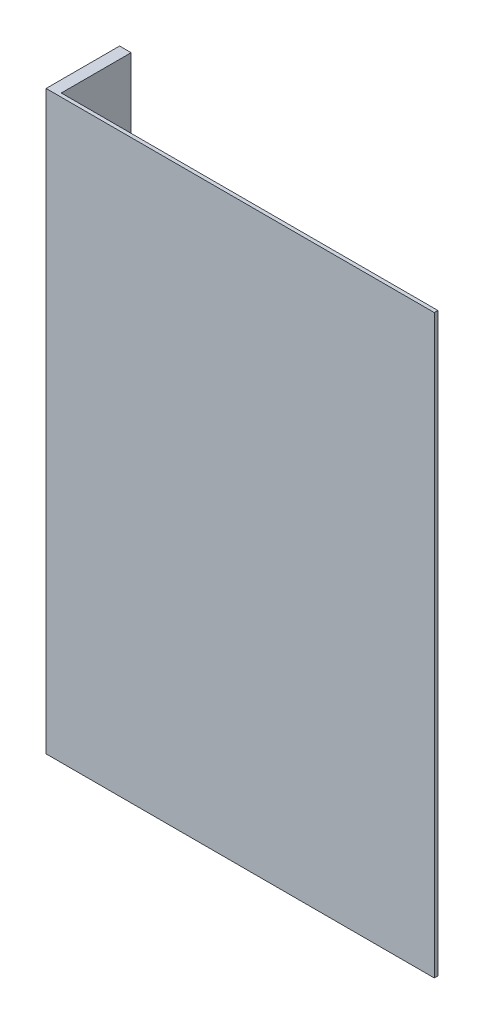
SolidWorks part; units mm, degrees
ref_plane "Front Plane" through (0, 0, 0) normal (0, 0, 1) x (1, 0, 0)
ref_plane "Top Plane" through (0, 0, 0) normal (0, 1, 0) x (1, 0, 0)
ref_plane "Right Plane" through (0, 0, 0) normal (1, 0, 0) x (0, 0, -1)
sketch "Sketch1" plane through (0, 0, 0) normal (0, 0, 1) x (1, 0, 0)
  line L0 (2.5917, 2.54) -> (2.5917, -124.46)
  line L7 (-72.4142, -124.46) -> (2.5917, -124.46)
  line L8 (2.5917, 2.54) -> (-72.4142, 2.54)
  line L9 (2.5917, 2.54) -> (-80.4142, 2.54) construction
  line L10 (-72.4142, 2.54) -> (-72.4142, -121.92)
  line L11 (2.5917, -121.92) -> (-80.4142, -121.92) construction
  line L12 (-72.4142, -121.92) -> (-72.4142, -124.46)
  dimension "D1" = 8
extrude "Boss-Extrude1" add sketch "Sketch1" along normal blind 0.8
sketch "Sketch2" plane through (0, 0, 0) normal (0, 0, 1) x (1, 0, 0)
  line L4 (-72.4142, 2.54) -> (-72.4142, -124.46) construction
  line L6 (-72.4142, -124.46) -> (-80.4142, -124.46)
  line L10 (-72.4142, -112.46) -> (-72.4142, -124.46)
  line L12 (-72.4142, 2.54) -> (-72.4142, -9.46)
  line L17 (-80.4142, -124.46) -> (-82.9542, -124.46)
  line L18 (-82.9542, -124.46) -> (-82.9542, -112.46)
  line L19 (-82.9542, -124.46) -> (-82.9542, -85.96) construction
  line L21 (-82.9542, 2.54) -> (-82.9542, -112.46)
  line L22 (-72.4142, 2.54) -> (-82.9542, 2.54)
  line L23 (-72.4142, -9.46) -> (-72.4142, -112.46)
extrude "Boss-Extrude2" add sketch "Sketch2" along normal blind 0.8
sketch "Sketch3" plane through (0, 0, 0) normal (0, 0, -1) x (-1, 0, 0)
  line L0 (82.9542, 2.54) -> (80.4142, 2.54)
  line L1 (80.4142, 2.54) -> (80.4142, 0) construction
  line L2 (-2.5917, 2.54) -> (82.9542, 2.54) construction
  line L3 (80.4142, 2.54) -> (80.4142, -9.46)
  line L6 (82.9542, -9.46) -> (82.9542, 2.54)
  line L7 (82.9542, -124.46) -> (80.4142, -124.46)
  line L8 (82.9542, -124.46) -> (-2.5917, -124.46) construction
  line L9 (80.4142, -121.92) -> (80.4142, -124.46) construction
  line L10 (80.4142, -124.46) -> (80.4142, -112.46)
  line L13 (82.9542, -112.46) -> (82.9542, -124.46)
  line L14 (80.4142, -9.46) -> (80.4142, -112.46)
  line L15 (82.9542, -9.46) -> (82.9542, -112.46)
extrude "Boss-Extrude3" add sketch "Sketch3" along normal up to surface (15.4 mm away) up to face at (2.5917, -60.96, 0.4)
